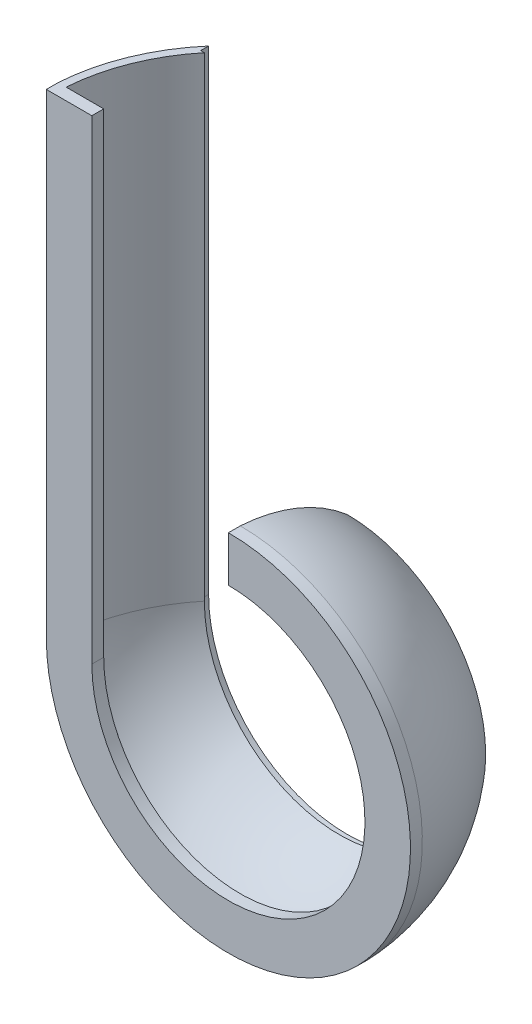
SolidWorks part; units mm, degrees
ref_plane "前视基准面" through (0, 0, 0) normal (0, 0, 1) x (1, 0, 0)
ref_plane "上视基准面" through (0, 0, 0) normal (0, 1, 0) x (1, 0, 0)
ref_plane "右视基准面" through (0, 0, 0) normal (1, 0, 0) x (0, 0, -1)
sketch "草图2" plane through (0, 0, 0) normal (0, 1, 0) x (1, 0, 0)
  line L2 (-34.5, 0) -> (-34.5, 3)
  line L13 (-43, 3) -> (-34.5, 3)
  line L17 (-46, 3) -> (-46, 0)
  line L18 (-46, 0) -> (-34.5, 0)
  line L21 (-43, 3) -> (-43.9956, 3)
  line L22 (-35, 30) -> (-35, 28)
  line L23 (-35, 28) -> (-34.0677, 28)
  arc A7 (-46, 3) -> (-35, 30) centre (0, 0) cw
  arc A9 (-34.0677, 28) -> (-43.9956, 3) centre (0, 0) ccw
ref_axis "基准轴1" through (0, 0, -42) along (0, 0, 1)
revolve "旋转2" add sketch "草图2" angle 270 about axis through (0, 0, -42) along (0, 0, 1)
extrude "凸台-拉伸1" add sketch "草图2<2>" along normal blind 120
sketch "草图2<2>" plane through (0, 0, 0) normal (0, 1, 0) x (1, 0, 0) same geometry as "草图2"
